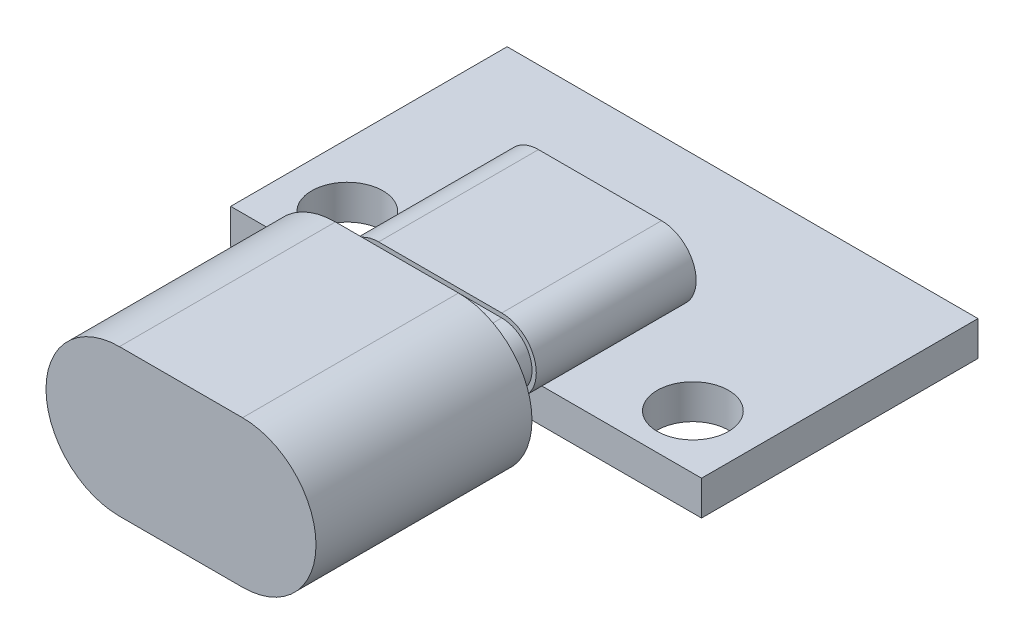
SolidWorks part; units mm, degrees
ref_plane "Front Plane" through (0, 0, 0) normal (0, 0, 1) x (1, 0, 0)
ref_plane "Top Plane" through (0, 0, 0) normal (0, 1, 0) x (1, 0, 0)
ref_plane "Right Plane" through (0, 0, 0) normal (1, 0, 0) x (0, 0, -1)
sketch "Sketch1" plane through (0, 0, 0) normal (0, 1, 0) x (1, 0, 0)
  line L1 (-10.9, -6.4) -> (10.9, -6.4)
  line L2 (-10.9, -6.4) -> (-10.9, 6.4)
  line L3 (-10.9, 6.4) -> (10.9, 6.4)
  line L4 (10.9, -6.4) -> (10.9, 6.4)
  line L5 (-10.9, -6.4) -> (10.9, 6.4) construction
  line L6 (-10.9, 6.4) -> (10.9, -6.4) construction
  point P0 (0, 0)
  dimension "D1" = 12.8
  dimension "D2" = 21.8
extrude "Boss-Extrude1" add sketch "Sketch1" along normal blind 1.6
sketch "Sketch2" plane through (0, 1.6, 0) normal (0, 1, 0) x (1, 0, 0)
  line L0 (-10.9, -3.9) -> (10.9, -3.9) construction
  line L1 (-10.9, 6.4) -> (-10.9, -6.4) construction
  line L2 (10.9, -6.4) -> (10.9, 6.4) construction
  line L3 (-10.9, -6.4) -> (10.9, -6.4) construction
  line L4 (-8, -3.9) -> (0, 0) construction
  line L5 (0, 0) -> (8, -3.9) construction
  circle A0 centre (-8, -3.9) radius 1.65
  circle A1 centre (8, -3.9) radius 1.65
  dimension "D1" = 3.3
  dimension "D2" = 16
  dimension "D3" = 2.5
extrude "Cut-Extrude1" cut sketch "Sketch2" against normal blind 1.6
ref_plane "Plane1" through (0, 0, 7.6) normal (0, 0, 1) x (1, 0, 0)
sketch "Sketch3" plane through (0, 0, 7.6) normal (0, 0, 1) x (1, 0, 0)
  line L0 (0, 0) -> (0, 3.2) construction
  line L1 (-2.85, 3.2) -> (2.85, 3.2) construction
  line L2 (-2.85, 4.8) -> (2.85, 4.8)
  line L3 (-2.85, 1.6) -> (2.85, 1.6)
  line L4 (-10.9, 1.6) -> (10.9, 1.6) construction
  arc A0 (-2.85, 4.8) -> (-2.85, 1.6) centre (-2.85, 3.2) ccw
  arc A1 (2.85, 1.6) -> (2.85, 4.8) centre (2.85, 3.2) ccw
  point P5 (0, 3.2)
  dimension "D1" = 8.9
  dimension "D2" = 3.2
extrude "Boss-Extrude2" add sketch "Sketch3" against normal blind 7.4
sketch "Sketch4" plane through (0, 0, 7.6) normal (0, 0, 1) x (1, 0, 0)
  line L4 (-2.85, 1.8) -> (2.85, 1.8)
  line L5 (2.85, 4.6) -> (-2.85, 4.6)
  line L6 (-2.85, 1.8) -> (2.85, 1.8)
  line L7 (2.85, 4.6) -> (-2.85, 4.6)
  arc A4 (-2.85, 4.6) -> (-2.85, 1.8) centre (-2.85, 3.2) ccw
  arc A5 (2.85, 1.8) -> (2.85, 4.6) centre (2.85, 3.2) ccw
  arc A6 (-2.85, 4.6) -> (-2.85, 1.8) centre (-2.85, 3.2) ccw
  arc A7 (2.85, 1.8) -> (2.85, 4.6) centre (2.85, 3.2) ccw
  dimension "D1" = 0.2
extrude "Boss-Extrude3" add sketch "Sketch4" along normal blind 2
sketch "Sketch5" plane through (0, 0, 9.6) normal (0, 0, 1) x (1, 0, 0)
  line L4 (-2.85, -0.2) -> (2.85, -0.2)
  line L5 (2.85, 6.6) -> (-2.85, 6.6)
  line L6 (-2.85, -0.2) -> (2.85, -0.2)
  line L7 (2.85, 6.6) -> (-2.85, 6.6)
  arc A4 (-2.85, 6.6) -> (-2.85, -0.2) centre (-2.85, 3.2) ccw
  arc A5 (2.85, -0.2) -> (2.85, 6.6) centre (2.85, 3.2) ccw
  arc A6 (-2.85, 6.6) -> (-2.85, -0.2) centre (-2.85, 3.2) ccw
  arc A7 (2.85, -0.2) -> (2.85, 6.6) centre (2.85, 3.2) ccw
  dimension "D3" = 12.5
  dimension "D2" = 6.8
  dimension "D1" = 2
extrude "Boss-Extrude4" add sketch "Sketch5" along normal blind 10
split "Split1" bodies to split 105 resulting bodies 106 107 split by face at (0, 3.2, 7.6)
